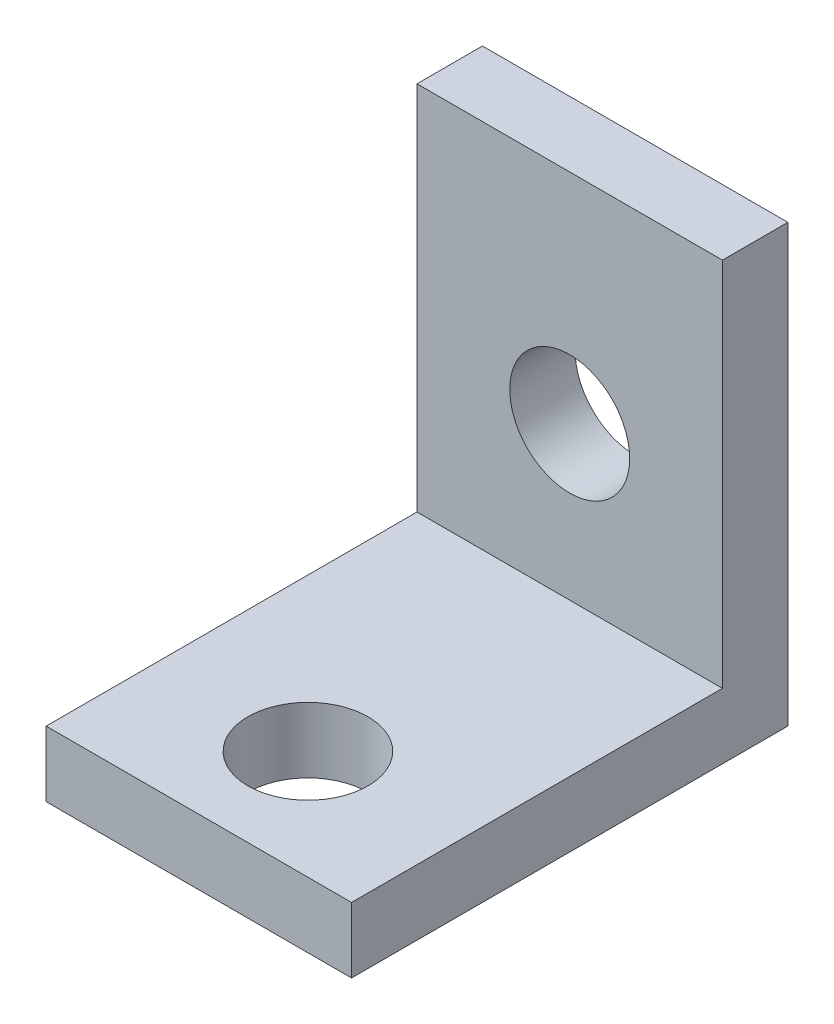
SolidWorks part; units mm, degrees
ref_plane "Front Plane" through (0, 0, 0) normal (0, 0, 1) x (1, 0, 0)
ref_plane "Top Plane" through (0, 0, 0) normal (0, 1, 0) x (1, 0, 0)
ref_plane "Right Plane" through (0, 0, 0) normal (1, 0, 0) x (0, 0, -1)
ref_plane "Plane1" through (0, 0, 0) normal (1, 0, 0) x (0, 0, -1)
sketch "Sketch1" plane through (0, 0, 0) normal (1, 0, 0) x (0, 0, -1)
  line L0 (-20, 0) -> (0, 0)
  line L1 (0, 0) -> (0, 20)
  line L2 (0, 20) -> (-3, 20)
  line L3 (-3, 20) -> (-3, 3)
  line L4 (-3, 3) -> (-20, 3)
  line L5 (-20, 3) -> (-20, 0)
extrude "Boss-Extrude1" add sketch "Sketch1" against normal blind 7 and the other way blind 7
ref_plane "Plane2" through (0, 0, 0) normal (0, 0, 1) x (1, 0, 0)
sketch "Sketch2" plane through (0, 0, 0) normal (0, 0, 1) x (1, 0, 0)
  circle A0 centre (0, 10) radius 2.75
extrude "Cut-Extrude1" cut sketch "Sketch2" along normal blind 3
ref_plane "Plane3" through (0, 0, 0) normal (0, 1, 0) x (1, 0, 0)
sketch "Sketch3" plane through (0, 0, 0) normal (0, 1, 0) x (1, 0, 0)
  circle A0 centre (0, -15) radius 2.75
extrude "Cut-Extrude2" cut sketch "Sketch3" along normal blind 3
